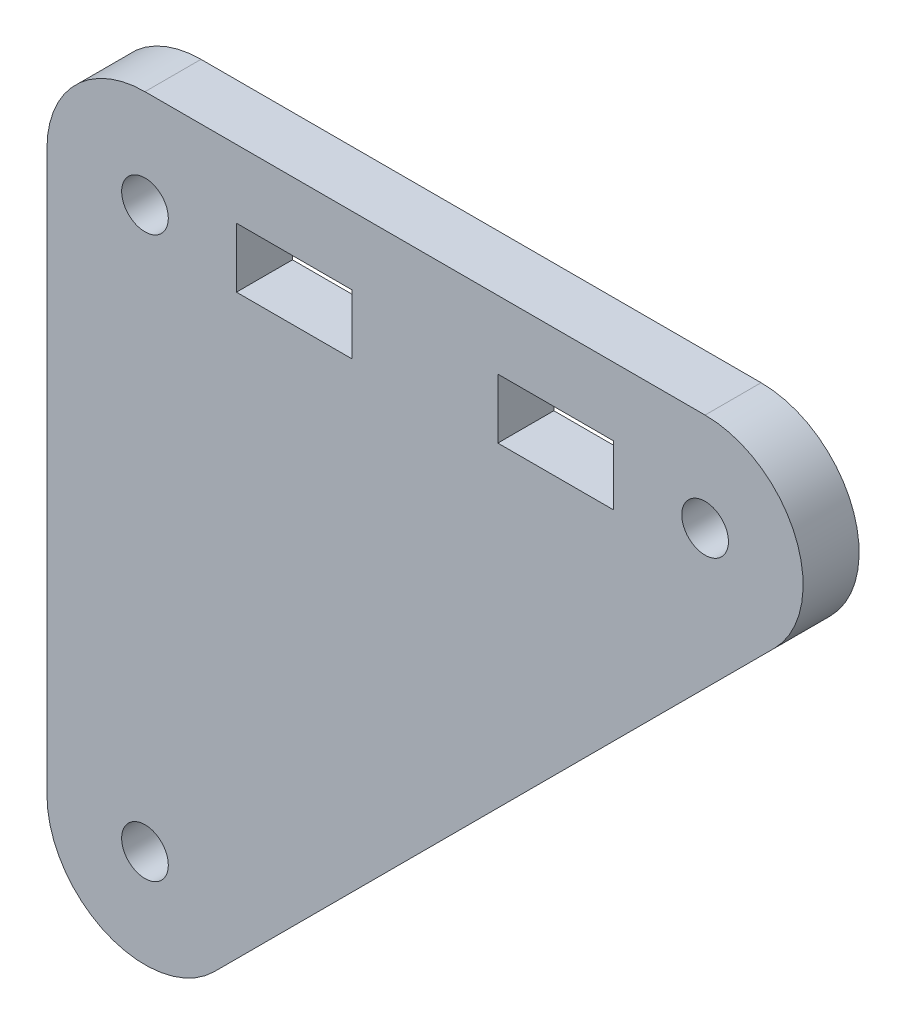
SolidWorks part; units mm, degrees
ref_plane "Plano frontal" through (0, 0, 0) normal (0, 0, 1) x (1, 0, 0)
ref_plane "Plano superior" through (0, 0, 0) normal (0, 1, 0) x (1, 0, 0)
ref_plane "Plano direito" through (0, 0, 0) normal (1, 0, 0) x (0, 0, -1)
sketch "Esboço1" plane through (0, 0, 0) normal (0, 0, 1) x (1, 0, 0)
  line L1 (-30, 30) -> (30, 30) construction
  line L2 (-30, 30) -> (-30, -30) construction
  line L3 (-30, -30) -> (30, -30) construction
  line L4 (30, 30) -> (30, -30) construction
  line L5 (-30, 30) -> (30, -30) construction
  line L6 (-30, -30) -> (30, 30) construction
  line L7 (-22.5754, -37.4246) -> (37.4246, 22.5754)
  line L8 (30, 40.5) -> (-30, 40.5)
  line L26 (-40.5, -30) -> (-40.5, 30)
  circle A0 centre (-30, 30) radius 2.5
  circle A1 centre (-30, -30) radius 2.5
  circle A2 centre (30, 30) radius 2.5
  arc A3 (-30, 40.5) -> (-40.5, 30) centre (-30, 30) ccw
  arc A4 (-40.5, -30) -> (-22.5754, -37.4246) centre (-30, -30) ccw
  arc A5 (37.4246, 22.5754) -> (30, 40.5) centre (30, 30) ccw
  circle A7 centre (30, 30) radius 10.5 construction
  circle A8 centre (-30, -30) radius 10.5 construction
  circle A9 centre (-30, 30) radius 10.5 construction
  point P0 (0, 0)
  point P13 (-20, 22.5)
  point P15 (-20, -22.5)
  point P20 (44, 0)
  point P34 (-81.0386, -15.474)
  point P36 (-81.0386, 15.2242)
  point P37 (-74.2886, -15.474)
  point P43 (-74.2886, 15.2242)
  dimension "D3" = 5
  dimension "D1" = 60
  dimension "D2" = 60
  dimension "D5" = 60
  dimension "D4" = 8
extrude "Ressalto-extrusão1" add sketch "Esboço1" along normal blind 6
ref_axis "Eixo1" through (-30, 30, 6) along (0, 0, -1)
ref_axis "Eixo2" through (30, 30, 6) along (0, 0, -1)
ref_plane "Plano1" through (0, 30, 0) normal (0, 1, 0) x (1, 0, 0)
sketch "Esboço3" plane through (0, 0, 6) normal (0, 0, 1) x (1, 0, 0)
  line L0 (20, 33) -> (20, 27) construction
  line L1 (20, 27) -> (8, 27) construction
  line L2 (8, 33) -> (8, 27) construction
  line L3 (20, 33) -> (8, 33) construction
  line L4 (-8, 33) -> (-8, 27) construction
  line L5 (-8, 27) -> (-20, 27) construction
  line L6 (-20, 33) -> (-20, 27) construction
  line L7 (-8, 33) -> (-20, 33) construction
  line L8 (20, 33) -> (20, 27) construction
  line L9 (20, 27) -> (8, 27) construction
  line L10 (8, 33) -> (8, 27) construction
  line L11 (20, 33) -> (8, 33) construction
  line L12 (-8, 33) -> (-8, 27) construction
  line L13 (-8, 27) -> (-20, 27) construction
  line L14 (-20, 33) -> (-20, 27) construction
  line L15 (-8, 33) -> (-20, 33) construction
  line L16 (20.2, 33.2) -> (20.2, 26.8)
  line L17 (20.2, 26.8) -> (7.8, 26.8)
  line L18 (7.8, 33.2) -> (7.8, 26.8)
  line L19 (20.2, 33.2) -> (7.8, 33.2)
  line L20 (-7.8, 33.2) -> (-7.8, 26.8)
  line L21 (-7.8, 26.8) -> (-20.2, 26.8)
  line L22 (-20.2, 33.2) -> (-20.2, 26.8)
  line L23 (-7.8, 33.2) -> (-20.2, 33.2)
  dimension "D1" = 0.2
extrude "Corte-extrusão1" cut sketch "Esboço3" against normal up to surface (6 mm away) up to face at (-10.8029, 10.8029, 0)
